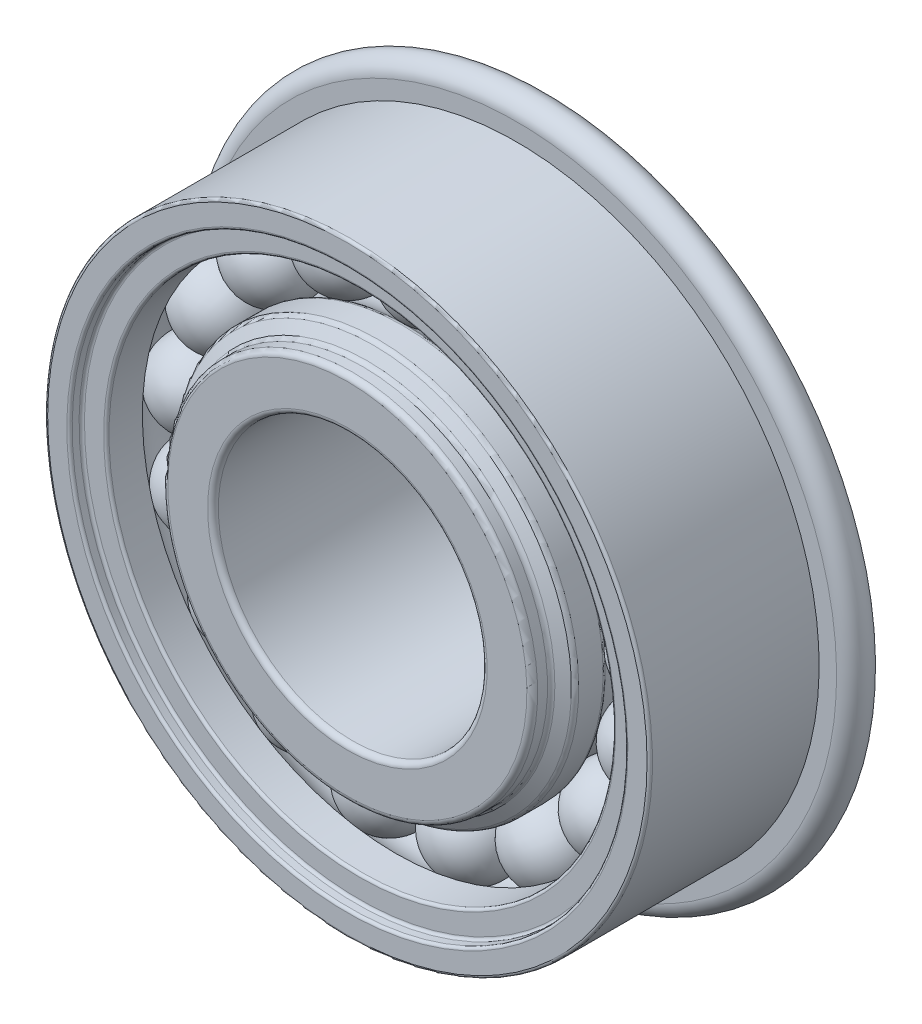
SolidWorks part; units mm, degrees
ref_plane "Front Plane" through (0, 0, 0) normal (0, 0, 1) x (1, 0, 0)
ref_plane "Top Plane" through (0, 0, 0) normal (0, 1, 0) x (1, 0, 0)
ref_plane "Right Plane" through (0, 0, 0) normal (1, 0, 0) x (0, 0, -1)
sketch "Sketch1" plane through (0, 0, 0) normal (1, 0, 0) x (0, 0, -1)
  line L0 (-5.5626, 0) -> (5.5626, 0) construction
  line L1 (3.9624, 0) -> (3.9624, 15.875)
  line L2 (3.9624, 15.875) -> (2.4384, 15.875)
  line L3 (2.4384, 15.875) -> (2.4384, 14.2875)
  line L4 (2.4384, 14.2875) -> (-5.5626, 14.2875)
  line L5 (-5.5626, 6.35) -> (3.9624, 6.35)
  line L6 (-5.5626, 8.7376) -> (5.5626, 8.7376)
  line L7 (-1.5621, 14.2875) -> (-1.5621, 10.3187) construction
  arc A0 (2.4384, 15.113) -> (3.9624, 15.113) centre (3.2004, 15.113) cw
  point P4 (0, 0)
  dimension "Inner Ring Width" = 11.1252
  dimension "Flange OD" = 31.75
  dimension "OD" = 28.575
  dimension "Width" = 9.525
  dimension "ID" = 12.7
  dimension "Inner Ring OD" = 17.4752
  dimension "Flange Thickness" = 1.524
  dimension "Ball Diameter" = 3.9688
  dimension "For Shaft Diameter" = 12.7
  dimension "For Housing ID" = 28.575
sketch "Sketch2" plane through (0, 0, 0) normal (1, 0, 0) x (0, 0, -1)
  line L0 (2.4384, 14.2875) -> (-5.5626, 14.2875) construction
  line L1 (2.4384, 14.2875) -> (-5.5626, 14.2875)
  line L2 (2.4384, 14.2875) -> (2.4384, 15.113)
  line L3 (3.9624, 15.113) -> (3.9624, 11.9682)
  line L4 (3.9624, 0) -> (3.9624, 15.875) construction
  line L5 (3.9624, 11.9682) -> (0.1564, 11.9682)
  line L6 (-4.9828, 11.9682) -> (-4.9828, 13.1278)
  line L7 (-4.9828, 13.1278) -> (-5.5626, 13.1278)
  line L8 (-5.5626, 13.1278) -> (-5.5626, 14.2875)
  line L9 (-1.5621, 12.9603) -> (-1.5621, 14.2875) construction
  line L10 (-1.5621, 6.35) -> (-1.5621, 7.5438) construction
  line L11 (-1.5621, 7.5438) -> (-1.5621, 8.7376) construction
  line L12 (-5.5626, 8.7376) -> (5.5626, 8.7376) construction
  line L13 (-5.5626, 6.35) -> (3.9624, 6.35) construction
  line L14 (-1.5621, 12.9603) -> (-1.5621, 11.9682) construction
  line L15 (-1.5621, 11.9682) -> (-1.5621, 10.976) construction
  line L16 (-3.2806, 11.9682) -> (-4.9828, 11.9682)
  line L17 (-4.4029, 13.1278) -> (-5.5626, 13.1278) construction
  arc A0 (3.9624, 15.113) -> (2.4384, 15.113) centre (3.2004, 15.113) ccw construction
  arc A1 (3.9624, 15.113) -> (2.4384, 15.113) centre (3.2004, 15.113) ccw
  circle A2 centre (-1.5621, 10.976) radius 1.9844 construction
  arc A3 (-3.2806, 11.9682) -> (0.1564, 11.9682) centre (-1.5621, 10.976) cw
  point P10 (-1.5621, 14.2875)
  point P12 (-1.5621, 8.9916)
  point P23 (-1.5621, 8.7376)
  point P24 (-1.5621, 11.9682)
  point P33 (-4.9828, 13.1278)
  dimension "D1" = 3.9688
  dimension "D2" = 0.254
revolve "Revolve1" add sketch "Sketch2" angle 360 about L0
sketch "Sketch3" plane through (0, 0, 0) normal (1, 0, 0) x (0, 0, -1)
  line L0 (-5.5626, 8.7376) -> (5.5626, 8.7376) construction
  line L1 (-5.5626, 8.7376) -> (-4.6965, 8.7376)
  line L2 (5.5626, 8.7376) -> (5.5626, 6.35)
  line L3 (5.5626, 6.35) -> (-5.5626, 6.35)
  line L4 (-5.5626, 6.35) -> (-5.5626, 8.7376)
  line L5 (2.4384, 8.7376) -> (5.5626, 8.7376)
  line L6 (-4.6965, 8.7376) -> (-4.2634, 9.4877)
  line L7 (-4.2634, 9.4877) -> (-2.8746, 9.4877)
  line L8 (-0.2496, 9.4877) -> (2.0053, 9.4877)
  line L9 (2.0053, 9.4877) -> (2.4384, 8.7376)
  line L10 (-1.5621, 10.976) -> (-1.5621, 9.9838) construction
  line L11 (-1.5621, 9.9838) -> (-1.5621, 8.9916) construction
  circle A2 centre (-1.5621, 10.976) radius 1.9844 construction
  arc A3 (-2.8746, 9.4877) -> (-0.2496, 9.4877) centre (-1.5621, 10.976) ccw
  point P12 (-1.5621, 9.4877)
  dimension "D1" = 60
  dimension "D2" = 60
revolve "Revolve2" add sketch "Sketch3" angle 360 about L0
sketch "Sketch5" plane through (0, 0, 0) normal (1, 0, 0) x (0, 0, -1)
  line L0 (5.5626, 6.9469) -> (5.5626, 6.35)
  line L2 (4.893, 6.385) -> (4.4927, 6.35)
  line L8 (5.3173, 7.0126) -> (5.5626, 6.9469) construction
  line L12 (5.5626, 8.7376) -> (5.5626, 6.35) construction
  line L13 (5.5626, 6.9469) -> (5.5626, 7.5438) construction
  line L14 (5.5626, 6.35) -> (-5.5626, 6.35) construction
  line L15 (4.4927, 6.35) -> (5.5626, 6.35)
  arc A0 (5.5626, 6.9469) -> (4.893, 6.385) centre (4.8266, 7.1441) cw
  dimension "D3" = 0.762
  dimension "D1" = 105
  dimension "D2" = 0.254
  dimension "D4" = 5
revolve "Cut-Revolve2" cut sketch "Sketch5" angle 360 about L0
sketch "Sketch6" plane through (0, 0, 0) normal (1, 0, 0) x (0, 0, -1)
  line L0 (5.3173, 7.0126) -> (5.5626, 6.9469) construction
  line L1 (5.3173, 7.0126) -> (5.5626, 6.9469)
  line L2 (5.3173, 7.0126) -> (5.5626, 7.9283) construction
  line L3 (5.5626, 8.7376) -> (5.5626, 6.35) construction
  line L4 (5.5626, 7.9283) -> (5.5626, 6.9469) construction
  line L5 (4.8708, 6.6381) -> (3.9624, 6.5586)
  line L6 (3.9624, 0) -> (3.9624, 15.875) construction
  line L7 (4.893, 6.385) -> (4.4927, 6.35) construction
  line L8 (3.9624, 6.5586) -> (3.9624, 6.6861)
  line L9 (5.1946, 7.0455) -> (5.5626, 7.0455)
  line L10 (4.8598, 6.7646) -> (3.9624, 6.6861)
  line L11 (5.5626, 7.0455) -> (5.5626, 6.9469)
  arc A1 (5.3173, 7.0126) -> (4.8708, 6.6381) centre (4.8266, 7.1441) cw
  arc A2 (4.8598, 6.7646) -> (5.1946, 7.0455) centre (4.8266, 7.1441) ccw
  arc A3 (4.893, 6.385) -> (5.5626, 6.9469) centre (4.8266, 7.1441) ccw construction
  dimension "D1" = 0.127
revolve "Cut-Revolve3" cut sketch "Sketch6" angle 360 about L0
fillet "Fillet4" radius 0.762 1 edges at (0, -7.0455, -5.5626)
sketch "Sketch7" plane through (0, 0, 0) normal (1, 0, 0) x (0, 0, -1)
  line L0 (5.5626, 7.5438) -> (5.5626, 8.1407) construction
  line L1 (5.5626, 8.7376) -> (5.5626, 6.35) construction
  line L2 (5.5626, 8.1407) -> (5.5626, 8.7376) construction
  line L3 (5.5626, 8.1407) -> (5.5626, 8.7376)
  line L4 (5.5626, 8.7376) -> (5.3636, 8.7376)
  line L5 (-5.5626, 8.7376) -> (5.5626, 8.7376) construction
  line L6 (5.3636, 8.7376) -> (5.3636, 8.5386)
  line L7 (5.3636, 8.5386) -> (5.3636, 8.3397)
  line L8 (5.3636, 8.3397) -> (5.3636, 8.1407)
  line L9 (5.3636, 8.1407) -> (5.5626, 8.1407)
revolve "Cut-Revolve4" cut sketch "Sketch7" angle 360 about L0
sketch "Sketch11" plane through (0, 0, 0) normal (1, 0, 0) x (0, 0, -1)
  line L0 (-1.5621, 12.9603) -> (-1.5621, 8.9916)
  circle A0 centre (-1.5621, 10.976) radius 1.9844 construction
  arc A1 (-1.5621, 8.9916) -> (-1.5621, 12.9603) centre (-1.5621, 10.976) ccw
revolve "Revolve3" add sketch "Sketch11" angle 360 about L0
pattern_circular "CirPattern3" count 17 over 360 about axis through (0, 0, 5.5626) along (0, 0, -1) of bodies 111
fillet "Fillet2" radius 0.127 2 edges at (0, -13.1278, 4.9828) (0, -11.9682, 4.9828)
fillet "Fillet3" radius 0.127 2 edges at (0, -14.2875, 5.5626) (0, -13.1278, 5.5626)
fillet "Fillet5" radius 0.254 9 edges at (0, -8.7376, -5.3636) (0, -8.7376, -2.4384) (0, -9.4877, 0.2496) (0, -9.4877, 2.8746) (0, -9.4877, 4.2634) (0, -8.7376, 4.6965) (0, -8.7376, 5.5626) (0, -6.35, 5.5626) (0, -8.1407, -5.5626)
sketch "Sketch12" plane through (0, 0, -3.9624) normal (0, 0, -1) x (-1, 0, 0)
  line L0 (0, 11.9682) -> (0, 15.113) construction
  circle A0 centre (0, 0) radius 11.9682 construction
  circle A1 centre (0, 0) radius 11.9682
  circle A2 centre (0, 0) radius 15.113 construction
  circle A3 centre (0, 0) radius 13.5406
  point P8 (0, 13.5406)
extrude "Cut-Extrude1" cut sketch "Sketch12" against normal blind 1.143
sketch "Sketch13" plane through (0, 0, 0) normal (0, 0, 1) x (1, 0, 0)
  circle A0 centre (0, 0) radius 8.7376
  circle A1 centre (0, 0) radius 15.875
  circle A2 centre (0, 0) radius 14.2875
  circle A3 centre (0, 0) radius 6.35
  point P0 (0, 8.7376)
  point P5 (0, 15.875)
  point P8 (0, 14.2875)
  point P11 (0, 6.35)
equation "\"D1@Sketch2\"=\"Ball Diameter@Sketch1\""
equation "\"D1@Cut-Extrude1\"=\"Flange Thickness@Sketch1\"*.75"
